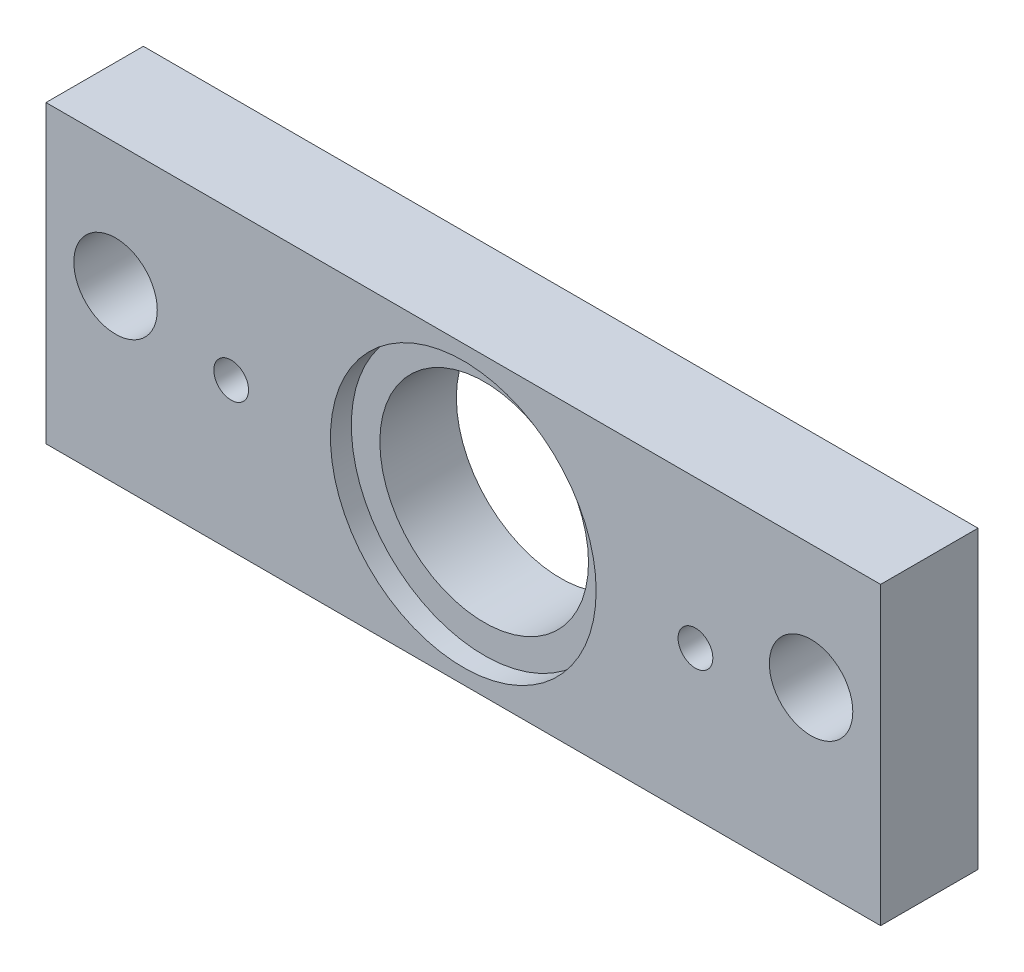
SolidWorks part; units mm, degrees
ref_plane "Front Plane" through (0, 0, 0) normal (0, 0, 1) x (1, 0, 0)
ref_plane "Top Plane" through (0, 0, 0) normal (0, 1, 0) x (1, 0, 0)
ref_plane "Right Plane" through (0, 0, 0) normal (1, 0, 0) x (0, 0, -1)
sketch "Sketch1" plane through (0, 0, 0) normal (0, 0, 1) x (1, 0, 0)
  line L1 (-60, -21.25) -> (60, -21.25)
  line L2 (-60, -21.25) -> (-60, 21.25)
  line L3 (-60, 21.25) -> (60, 21.25)
  line L4 (60, -21.25) -> (60, 21.25)
  line L5 (-60, -21.25) -> (60, 21.25) construction
  line L6 (-60, 21.25) -> (60, -21.25) construction
  point P0 (0, 0)
  dimension "D1" = 120
  dimension "D2" = 42.5
extrude "Boss-Extrude1" add sketch "Sketch1" along normal mid plane 14
sketch "Sketch2" plane through (0, 0, 7) normal (0, 0, 1) x (1, 0, 0)
  circle A0 centre (0, 0) radius 19.1
  dimension "D1" = 38.2
extrude "Cut-Extrude1" cut sketch "Sketch2" against normal blind 3
sketch "Sketch3" plane through (0, 0, 4) normal (0, 0, 1) x (1, 0, 0)
  circle A0 centre (0, 0) radius 15
extrude "Cut-Extrude2" cut sketch "Sketch3" against normal through all
sketch "Sketch4" plane through (0, 0, 7) normal (0, 0, 1) x (1, 0, 0)
  circle A0 centre (-33.375, 0) radius 2.5
  circle A1 centre (33.375, 0) radius 2.5
  dimension "D1" = 5
  dimension "D2" = 5
  dimension "D3" = 33.375
  dimension "D4" = 33.375
extrude "Cut-Extrude3" cut sketch "Sketch4" against normal through all
sketch "Sketch5" plane through (0, 0, 7) normal (0, 0, 1) x (1, 0, 0)
  line L0 (-40.6477, 3.4) -> (36.4799, 3.4) construction
  circle A0 centre (-50, 3.4) radius 6
  circle A1 centre (50, 3.4) radius 6
  dimension "D1" = 12
  dimension "D2" = 12
  dimension "D4" = 50
  dimension "D3" = 50
  dimension "D5" = 3.4
extrude "Cut-Extrude4" cut sketch "Sketch5" against normal through all
sketch "Sketch6" plane through (0, -21.25, 0) normal (0, -1, 0) x (1, 0, 0)
  line L0 (-60, 0) -> (60, 0) construction
  line L1 (-60, 7) -> (-60, -7) construction
  line L2 (60, 7) -> (60, -7) construction
  circle A0 centre (-50, 0) radius 2.5
  circle A1 centre (-25, 0) radius 2.5
  circle A2 centre (25, 0) radius 2.5
  circle A3 centre (50, 0) radius 2.5
  circle A4 centre (-37.5, 0) radius 1.25
  circle A5 centre (37.5, 0) radius 1.25
  dimension "D1" = 5
  dimension "D2" = 5
  dimension "D3" = 5
  dimension "D4" = 5
  dimension "D5" = 10
  dimension "D9" = 2.5
  dimension "D10" = 2.5
  dimension "D11" = 22.5
  dimension "D12" = 22.5
  dimension "D6" = 35
  dimension "D7" = 10
  dimension "D8" = 35
extrude "Cut-Extrude5" cut sketch "Sketch6" against normal blind 10
equation "\"D4@Sketch4\"=\"D3@Sketch4\""
